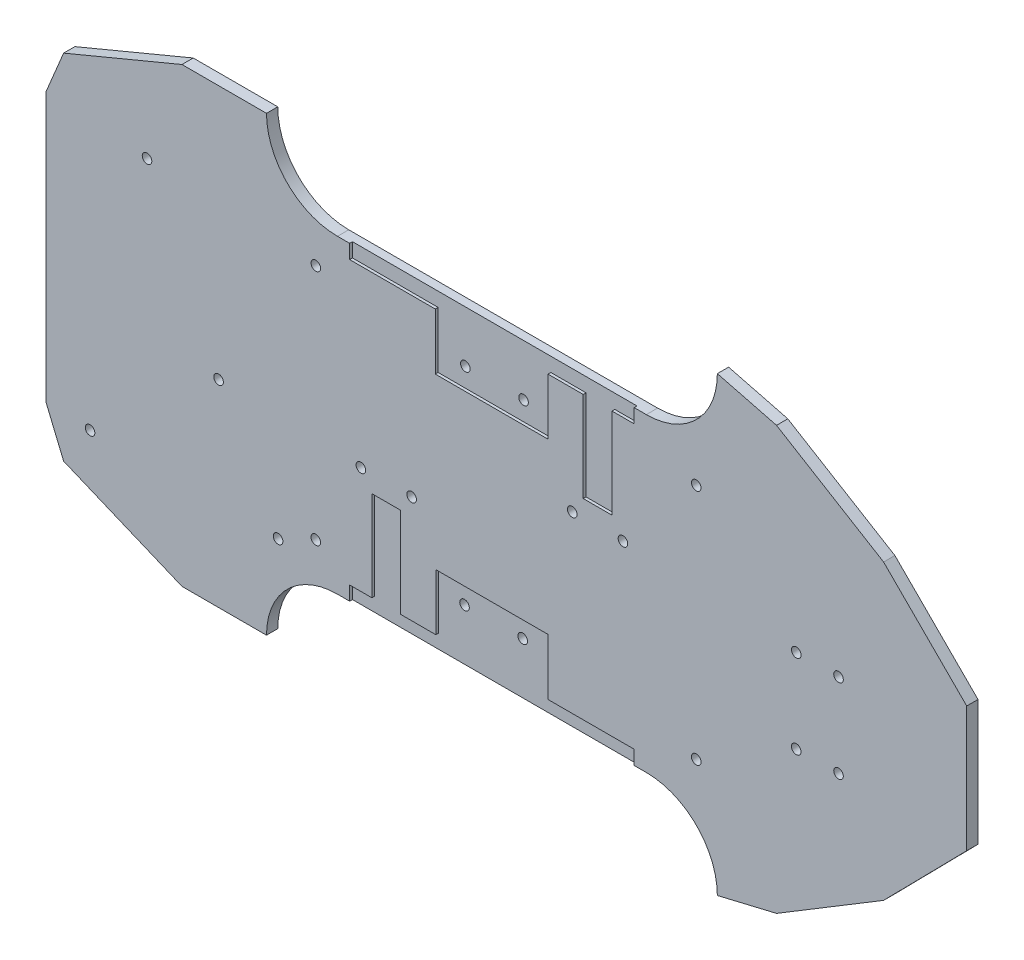
SolidWorks part; units mm, degrees
material "ABS PC"
ref_plane "Plan de face" through (0, 0, 0) normal (0, 0, 1) x (1, 0, 0)
ref_plane "Plan de dessus" through (0, 0, 0) normal (0, 1, 0) x (1, 0, 0)
ref_plane "Plan de droite" through (0, 0, 0) normal (1, 0, 0) x (0, 0, -1)
sketch "Esquisse1" plane through (0, 0, 0) normal (0, 0, 1) x (1, 0, 0)
  line L0 (-87.472, 59.5843) -> (-117.472, 59.5843)
  line L1 (-87.472, -100.8157) -> (-117.472, -100.8157)
  line L2 (-117.472, -100.8157) -> (-159.472, -83.3157)
  line L3 (-159.472, -83.3157) -> (-165.722, -68.3157)
  line L4 (72.528, -100.8157) -> (93.528, -95.8157)
  line L5 (-165.722, -68.3157) -> (-165.722, 27.0843)
  line L7 (-62.272, 34.3843) -> (47.328, 34.3843)
  line L8 (93.528, -95.8157) -> (131.528, -72.8157)
  line L9 (-165.722, 27.0843) -> (-159.472, 42.0843)
  line L10 (131.528, -72.8157) -> (161.028, -42.8157)
  line L11 (161.028, -42.8157) -> (161.028, 1.6843)
  line L12 (161.028, 1.6843) -> (131.528, 31.1843)
  line L13 (-62.272, -75.6157) -> (47.328, -75.6157)
  line L14 (131.528, 31.1843) -> (93.528, 54.1843)
  line L15 (93.528, 54.1843) -> (72.528, 59.5843)
  line L16 (-159.472, 42.0843) -> (-117.472, 59.5843)
  arc A4 (-87.472, 59.5843) -> (-62.272, 34.3843) centre (-62.272, 59.5843) ccw
  arc A5 (-87.472, -100.8157) -> (-62.272, -75.6157) centre (-62.272, -100.8157) cw
  arc A6 (72.528, -100.8157) -> (47.328, -75.6157) centre (47.328, -100.8157) ccw
  arc A7 (72.528, 59.5843) -> (47.328, 34.3843) centre (47.328, 59.5843) cw
  point P7 (72.528, 59.5843)
  point P33 (161.028, -42.8157)
  point P37 (161.028, 1.6843)
  point P39 (93.528, -95.8157)
  dimension "D16" = 102.5
  dimension "D17" = 59
  dimension "D18" = 72
  dimension "D19" = 17.5
  dimension "D9" = 25.2
  dimension "D28" = 25.2
  dimension "D25" = 25.2
  dimension "D30" = 25.2
  dimension "D8" = 59
  dimension "D22" = 132
  dimension "D12" = 30
  dimension "D20" = 72
  dimension "D33" = 109.6
  dimension "D4" = 25.2
  dimension "D5" = 25.2
  dimension "D6" = 5
  dimension "D7" = 21
  dimension "D10" = 160
  dimension "D11" = 28
  dimension "D13" = 58
  dimension "D14" = 88.5
  dimension "D15" = 30
  dimension "D21" = 160
  dimension "D23" = 109.6
  dimension "D24" = 17.5
  dimension "D26" = 155
  dimension "D27" = 25.2
  dimension "D29" = 15
  dimension "D31" = 25.2
  dimension "D32" = 15
  dimension "D34" = 21
  dimension "D37" = 110
extrude "Boss.-Extru.1" add sketch "Esquisse1" along normal blind 4
hole_wizard "Dégagement M2.51" positions "Esquisse5" profile "Esquisse4" hole size "M2.5" standard "ISO"
sketch "Esquisse5" plane through (0, 0, 0) normal (0, 0, -1) x (-1, 0, 0)
  circle A0 centre (-21.028, -8.6656) radius 1.025 construction
  point P0 (-21.028, -8.6656)
  point P1 (-39.028, -8.6656)
  point P4 (35.972, -32.5657)
  point P7 (53.972, -32.5657)
sketch "Esquisse4" plane through (21.028, -8.6656, 0) normal (1, 0, 0) x (0, 1, 0)
  line L0 (0, 0) -> (0, 5.8712)
  line L1 (0, 5.8712) -> (1.45, 5)
  line L2 (1.45, 5) -> (1.45, 0)
  line L5 (1.45, 0) -> (0, 0)
  line L10 (0, 5.8712) -> (-1.45, 5) construction
  line L11 (0, -6.35) -> (0, 107.95) construction
  dimension "Diamètre du perçage" = 2.9
  dimension "Profondeur du perçage" = 5
  dimension "Angle de pointe" = 118
hole_wizard "Dégagement M31" positions "Esquisse7" profile "Esquisse6" hole size "M3" standard "ISO"
sketch "Esquisse7" plane through (0, 0, 0) normal (0, 0, -1) x (-1, 0, 0)
  point P1 (17.8966, 16.1343)
  point P4 (-2.7526, 16.1343)
  point P13 (53.972, -32.5657)
  point P16 (35.972, -32.5657)
  point P19 (18.1966, -57.3657)
  point P22 (-2.4526, -57.3657)
  point P28 (-39.028, -8.6656)
  point P31 (-21.028, -8.6656)
sketch "Esquisse6" plane through (-17.8966, 16.1343, 0) normal (1, 0, 0) x (0, 1, 0)
  line L0 (0, 0) -> (0, 7.0215)
  line L1 (0, 7.0215) -> (1.7, 6)
  line L2 (1.7, 6) -> (1.7, 0)
  line L5 (1.7, 0) -> (0, 0)
  line L10 (0, 7.0215) -> (-1.7, 6) construction
  line L11 (0, -6.35) -> (0, 107.95) construction
  dimension "Diamètre du perçage" = 3.4
  dimension "Profondeur du perçage" = 6
  dimension "Angle de pointe" = 118
hole_wizard "Dégagement M32" positions "Esquisse9" profile "Esquisse8" hole size "M3" standard "ISO"
sketch "Esquisse9" plane through (0, 0, 0) normal (0, 0, -1) x (-1, 0, 0)
  point P1 (69.972, -62.7289)
  point P4 (69.972, 21.4976)
  point P7 (-65.028, -62.7289)
  point P10 (-65.028, 21.4976)
sketch "Esquisse8" plane through (-69.972, -62.7289, 0) normal (1, 0, 0) x (0, 1, 0)
  line L0 (0, 0) -> (0, 6.0215)
  line L1 (0, 6.0215) -> (1.7, 5)
  line L2 (1.7, 5) -> (1.7, 0)
  line L5 (1.7, 0) -> (0, 0)
  line L10 (0, 6.0215) -> (-1.7, 5) construction
  line L11 (0, -6.35) -> (0, 107.95) construction
  dimension "Diamètre du perçage" = 3.4
  dimension "Profondeur du perçage" = 5
  dimension "Angle de pointe" = 118
sketch "Esquisse10" plane through (0, 0, 4) normal (0, 0, 1) x (1, 0, 0)
  line L0 (43.028, 34.3843) -> (43.028, 29.3843)
  line L1 (43.028, 29.3843) -> (35.128, 29.3843)
  line L2 (35.128, 29.3843) -> (35.128, -2.6157)
  line L3 (35.128, -2.6157) -> (24.928, -2.6157)
  line L4 (24.928, -2.6157) -> (24.928, 29.3843)
  line L5 (24.928, 29.3843) -> (12.428, 29.3843)
  line L8 (12.428, 29.3843) -> (12.428, 9.3843)
  line L9 (12.428, 9.3843) -> (-27.572, 9.3843)
  line L10 (-27.572, 9.3843) -> (-27.572, 29.3843)
  line L11 (-76.472, 29.3843) -> (71.528, 29.3843) construction
  line L12 (-27.572, 29.3843) -> (-57.972, 29.3843)
  line L13 (-57.972, 29.3843) -> (-57.972, 34.3843)
  line L15 (-57.972, 34.3843) -> (-57.972, 29.3843) construction
  line L16 (-57.972, 34.3843) -> (43.028, 34.3843)
  line L17 (43.028, 34.3843) -> (42.9276, 34.4822)
  line L18 (43.028, -75.6157) -> (43.028, -70.6157)
  line L19 (43.028, -70.6157) -> (12.4203, -70.6157)
  line L20 (12.4203, -70.6157) -> (12.4203, -50.6157)
  line L21 (12.4203, -50.6157) -> (-27.372, -50.6157)
  line L22 (-27.372, -50.6157) -> (-27.372, -70.6157)
  line L23 (71.528, -70.6157) -> (-76.472, -70.6157) construction
  line L24 (-27.372, -70.6157) -> (-36.072, -70.6157)
  line L25 (-36.072, -70.6157) -> (-39.872, -70.6157)
  line L26 (-39.872, -70.6157) -> (-39.872, -38.6157)
  line L27 (-39.872, -38.6157) -> (-50.072, -38.6157)
  line L28 (-50.072, -38.6157) -> (-50.072, -70.6157)
  line L29 (-50.072, -70.6157) -> (-57.972, -70.6157)
  line L30 (-57.972, -70.6157) -> (-57.972, -75.6157)
  line L31 (-57.972, -75.6157) -> (43.028, -75.6157)
  line L32 (43.028, -75.6157) -> (43.028, -75.7928)
  dimension "D1" = 40
  dimension "D2" = 32
  dimension "D3" = 12.5
  dimension "D4" = 32
  dimension "D5" = 12.5
  dimension "D6" = 20
extrude "Enlèv. mat.-Extru.1" cut sketch "Esquisse10" against normal blind 1 contours L18 L19 L20 L21 L22 L24 L25 L26 L27 L28 L29 L30 L31
extrude "Enlèv. mat.-Extru.2" cut sketch "Esquisse10<3>" against normal blind 1 contours L13 L12 L10 L9 L8 L5 L4 L3 L2 L1 L0 region at (-0.0183, 22.0533, 4)
sketch "Esquisse10<3>" plane through (0, 0, 4) normal (0, 0, 1) x (1, 0, 0) same geometry as "Esquisse10"
hole_wizard "Dégagement M33" positions "Esquisse13" profile "Esquisse12" hole size "M3" standard "ISO"
sketch "Esquisse13" plane through (0, 0, 0) normal (0, 0, -1) x (-1, 0, 0)
  point P1 (104.4714, -30.7157)
  point P3 (129.8714, 24.4843)
sketch "Esquisse12" plane through (-104.4714, -30.7157, 0) normal (1, 0, 0) x (0, 1, 0)
  line L0 (0, 0) -> (0, 7.0215)
  line L1 (0, 7.0215) -> (1.7, 6)
  line L2 (1.7, 6) -> (1.7, 0)
  line L5 (1.7, 0) -> (0, 0)
  line L10 (0, 7.0215) -> (-1.7, 6) construction
  line L11 (0, -6.35) -> (0, 107.95) construction
  dimension "Diamètre du perçage" = 3.4
  dimension "Profondeur du perçage" = 6
  dimension "Angle de pointe" = 118
sketch "Esquisse14" plane through (0, 0, 4) normal (0, 0, 1) x (1, 0, 0)
  line L0 (-166.4714, -20.6163) -> (141.528, -20.6163) construction
ref_plane "Plan1" through (0, -20.6163, 0) normal (0, -1, 0) x (1, 0, 0)
hole_wizard "Dégagement M34" positions "Esquisse16" profile "Esquisse15" hole size "M3" standard "ISO"
sketch "Esquisse16" plane through (0, 0, 0) normal (0, 0, -1) x (-1, 0, 0)
  point P1 (-100.528, -41.8157)
  point P3 (-115.528, -41.8157)
  point P5 (-100.528, -12.1157)
  point P7 (-115.528, -12.1157)
sketch "Esquisse15" plane through (100.528, -41.8157, 0) normal (1, 0, 0) x (0, 1, 0)
  line L0 (0, 0) -> (0, 6.0215)
  line L1 (0, 6.0215) -> (1.7, 5)
  line L2 (1.7, 5) -> (1.7, 0)
  line L5 (1.7, 0) -> (0, 0)
  line L10 (0, 6.0215) -> (-1.7, 5) construction
  line L11 (0, -6.35) -> (0, 107.95) construction
  dimension "Diamètre du perçage" = 3.4
  dimension "Profondeur du perçage" = 5
  dimension "Angle de pointe" = 118
hole_wizard "Dégagement M35" positions "Esquisse18" profile "Esquisse17" hole size "M3" standard "ISO"
sketch "Esquisse18" plane through (0, 0, 0) normal (0, 0, -1) x (-1, 0, 0)
  point P1 (150.0853, -69.1157)
  point P3 (83.3588, -69.1157)
sketch "Esquisse17" plane through (-150.0853, -69.1157, 0) normal (1, 0, 0) x (0, 1, 0)
  line L0 (0, 0) -> (0, 6.0215)
  line L1 (0, 6.0215) -> (1.7, 5)
  line L2 (1.7, 5) -> (1.7, 0)
  line L5 (1.7, 0) -> (0, 0)
  line L10 (0, 6.0215) -> (-1.7, 5) construction
  line L11 (0, -6.35) -> (0, 107.95) construction
  dimension "Diamètre du perçage" = 3.4
  dimension "Profondeur du perçage" = 5
  dimension "Angle de pointe" = 118
